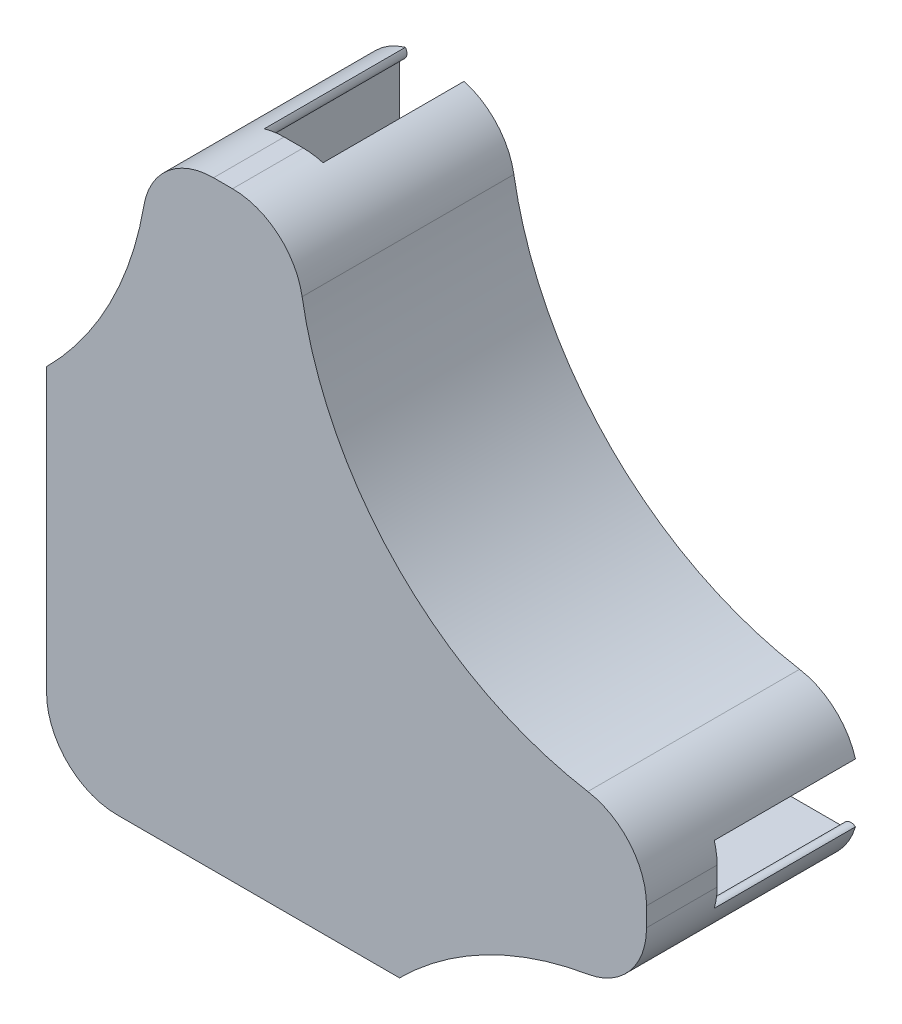
SolidWorks part; units mm, degrees
ref_plane "Front Plane" through (0, 0, 0) normal (0, 0, 1) x (1, 0, 0)
ref_plane "Top Plane" through (0, 0, 0) normal (0, 1, 0) x (1, 0, 0)
ref_plane "Right Plane" through (0, 0, 0) normal (1, 0, 0) x (0, 0, -1)
sketch "Sketch2" plane through (0, 0, 0) normal (0, 0, 1) x (1, 0, 0)
  line L0 (0, 12.7) -> (0, -12.7) construction
  line L1 (-12.7, 0) -> (12.7, 0) construction
  line L2 (3.2512, -12.7) -> (12.7, -12.7)
  line L3 (12.7, -12.7) -> (12.7, -3.2512)
  line L4 (3.2512, -12.7) -> (3.2512, -10.4902)
  line L5 (3.2512, -10.4902) -> (8.9276, -10.4902)
  line L6 (8.9276, -10.4902) -> (3.0856, -4.6482)
  line L7 (0, 0) -> (12.7, -12.7) construction
  line L8 (12.7, -3.2512) -> (10.4902, -3.2512)
  line L9 (10.4902, -3.2512) -> (10.4902, -8.9276)
  line L10 (10.4902, -8.9276) -> (4.6482, -3.0856)
  circle A0 centre (0, 0) radius 2.6035
  arc A1 (6.3485, -10.4902) -> (7.1039, -8.6665) centre (6.3485, -9.4219) ccw construction
  point P8 (0, -4.6482)
  dimension "Center Hole Diameter" = 5.207
  dimension "Rail Height" = 25.4
  dimension "Rail Width" = 25.4
  dimension "T-Slot Width" = 6.5024
  dimension "Slot Inner Width" = 14.8336
  dimension "Thickness" = 2.2098
  dimension "Slot Depth" = 5.842
  dimension "D1" = 2.2098
sketch "Sketch3" plane through (0, 0, 0) normal (1, 0, 0) x (0, 0, -1)
  line L0 (-139.7, -12.7) -> (139.7, -12.7) construction
  line L1 (-114.3, 0) -> (114.3, 0) construction
  dimension "D1" = 25.4
  dimension "Length" = 279.4
sketch "Sketch4" plane through (0, 0, 0) normal (0, 0, 1) x (1, 0, 0)
  line L0 (4.1904, -12.7) -> (10.1173, -12.7)
  line L1 (3.2512, -12.7) -> (12.7, -12.7) construction
  line L2 (3.2512, -12.7) -> (3.2512, -10.4902) construction
  line L3 (3.2512, -10.4902) -> (8.9276, -10.4902) construction
  line L4 (3.2512, -11.4294) -> (3.2512, -11.7608) construction
  line L5 (4.1904, -10.4902) -> (6.3485, -10.4902) construction
  line L6 (0, -4.6482) -> (2.164, -4.6482) construction
  line L7 (8.9276, -10.4902) -> (3.0856, -4.6482) construction
  line L8 (3.7373, -5.2999) -> (7.1039, -8.6665) construction
  line L9 (12.7, -12.7) -> (12.7, -3.2512) construction
  line L10 (10.4902, -8.9276) -> (4.6482, -3.0856) construction
  line L11 (10.4902, -3.2512) -> (10.4902, -8.9276) construction
  line L12 (10.4902, -6.3485) -> (10.4902, -4.1904) construction
  line L13 (12.7, -3.2512) -> (10.4902, -3.2512) construction
  line L14 (11.4294, -3.2512) -> (11.7608, -3.2512) construction
  line L15 (12.7, -4.1904) -> (12.7, -10.1173)
  line L16 (8.6665, -7.1039) -> (5.2999, -3.7373) construction
  line L17 (4.6482, 0) -> (4.6482, -2.164) construction
  line L18 (-12.7, 0) -> (12.7, 0) construction
  line L19 (0, -4.6482) -> (0, -2.6035) construction
  line L20 (0, 12.7) -> (0, -12.7) construction
  line L21 (4.6482, 0) -> (2.6035, 0) construction
  line L22 (4.1904, -13.335) -> (10.1173, -13.335) construction
  line L23 (13.335, -4.1904) -> (13.335, -10.1173) construction
  line L24 (11.4294, -2.6162) -> (11.7608, -2.6162)
  line L25 (9.8552, -6.3485) -> (9.8552, -4.1904)
  line L26 (9.1155, -6.6549) -> (5.7489, -3.2883)
  line L27 (5.2832, 0.635) -> (5.2832, -2.164)
  line L28 (5.2832, 0.635) -> (1.8633, 0.635)
  line L29 (-0.635, -5.2832) -> (-0.635, -1.8633)
  line L30 (-0.635, -5.2832) -> (2.164, -5.2832)
  line L31 (3.2883, -5.7489) -> (6.6549, -9.1155)
  line L32 (4.1904, -9.8552) -> (6.3485, -9.8552)
  line L33 (2.6162, -11.4294) -> (2.6162, -11.7608)
  line L34 (2.6162, -11.7608) -> (2.6162, -12.7)
  line L35 (2.6162, -12.7) -> (4.1904, -12.7)
  line L36 (12.7, -4.1904) -> (12.7, -2.6162)
  line L37 (11.7608, -2.6162) -> (12.7, -2.6162)
  line L38 (11.4294, -2.6162) -> (9.8552, -2.6162)
  line L41 (2.6162, -9.8552) -> (2.6162, -11.4294)
  line L42 (10.1173, -12.7) -> (12.7, -12.7)
  line L43 (12.7, -12.7) -> (12.7, -10.1173)
  line L44 (9.8552, -2.6162) -> (9.8552, -4.1904)
  line L45 (4.1904, -9.8552) -> (2.6162, -9.8552)
  arc A0 (3.2512, -11.7608) -> (4.1904, -12.7) centre (4.1904, -11.7608) ccw construction
  arc A1 (10.1173, -13.335) -> (13.335, -10.1173) centre (10.1173, -10.1173) ccw construction
  arc A2 (3.2512, -11.4294) -> (4.1904, -10.4902) centre (4.1904, -11.4294) cw construction
  arc A3 (6.3485, -10.4902) -> (7.1039, -8.6665) centre (6.3485, -9.4219) ccw construction
  arc A4 (2.164, -4.6482) -> (3.7373, -5.2999) centre (2.164, -6.8732) cw construction
  arc A5 (10.1173, -12.7) -> (12.7, -10.1173) centre (10.1173, -10.1173) ccw construction
  arc A6 (8.6665, -7.1039) -> (10.4902, -6.3485) centre (9.4219, -6.3485) ccw construction
  arc A7 (10.4902, -4.1904) -> (11.4294, -3.2512) centre (11.4294, -4.1904) cw construction
  arc A8 (11.7608, -3.2512) -> (12.7, -4.1904) centre (11.7608, -4.1904) cw construction
  arc A9 (5.2999, -3.7373) -> (4.6482, -2.164) centre (6.8732, -2.164) cw construction
  circle A10 centre (0, 0) radius 2.6035 construction
  arc A11 (0, -2.6035) -> (2.6035, 0) centre (0, 0) ccw construction
  arc A12 (11.7608, -2.6162) -> (13.335, -4.1904) centre (11.7608, -4.1904) cw construction
  arc A13 (9.8552, -4.1904) -> (11.4294, -2.6162) centre (11.4294, -4.1904) cw construction
  arc A14 (9.1155, -6.6549) -> (9.8552, -6.3485) centre (9.4219, -6.3485) ccw
  arc A15 (5.7489, -3.2883) -> (5.2832, -2.164) centre (6.8732, -2.164) cw
  arc A16 (-0.635, -1.8633) -> (1.8633, 0.635) centre (0, 0) ccw
  arc A17 (2.164, -5.2832) -> (3.2883, -5.7489) centre (2.164, -6.8732) cw
  arc A18 (6.3485, -9.8552) -> (6.6549, -9.1155) centre (6.3485, -9.4219) ccw
  arc A19 (2.6162, -11.4294) -> (4.1904, -9.8552) centre (4.1904, -11.4294) cw construction
  arc A20 (2.6162, -11.7608) -> (4.1904, -13.335) centre (4.1904, -11.7608) ccw construction
  dimension "D1" = 2.5827
  dimension "D2" = 2.225
  dimension "D3" = 0.9392
  dimension "D4" = 0.635
sketch "Sketch5" plane through (0, 0, 0) normal (0, 0, 1) x (1, 0, 0)
  line L0 (12.7, -4.1904) -> (12.7, -10.1173) construction
  line L1 (-15.875, 15.875) -> (15.875, 15.875) construction
  line L2 (-15.875, 15.875) -> (-15.875, -15.875)
  line L3 (-15.875, -15.875) -> (15.875, -15.875)
  line L4 (15.875, 15.875) -> (15.875, -15.875) construction
  line L5 (-15.875, 15.875) -> (15.875, -15.875) construction
  line L6 (-15.875, -15.875) -> (15.875, 15.875) construction
  line L8 (-6.6691, 38.1) -> (6.6691, 38.1)
  line L10 (38.1, -6.6691) -> (38.1, 6.6691)
  line L11 (6.6691, 38.1) -> (6.6691, 15.875) construction
  line L12 (38.1, 6.6691) -> (15.875, 6.6691) construction
  line L13 (-6.6691, 38.1) -> (-6.6691, 15.875) construction
  line L14 (38.1, -6.6691) -> (15.875, -6.6691) construction
  line L15 (0, 38.1) -> (0, 15.875) construction
  line L16 (38.1, 0) -> (15.875, 0) construction
  arc A0 (6.6691, 38.1) -> (38.1, 6.6691) centre (38.1, 38.1) ccw
  arc A1 (-6.6691, 38.1) -> (-15.875, 15.875) centre (-38.1, 38.1) cw
  arc A2 (38.1, -6.6691) -> (15.875, -15.875) centre (38.1, -38.1) ccw
  point P0 (0, 0)
  dimension "D1" = 3.175
  dimension "D2" = 25.4
extrude "Boss-Extrude1" add sketch "Sketch5" along normal blind 19.05 contours L8 A0 L10 A2 L3 L2 A1
extrude "Cut-Extrude1" cut sketch "Sketch4" along normal blind 12.7
mirror "Mirror1" about plane through (0, 0, 0) normal (0, 1, 0) of "Cut-Extrude1"
mirror "Mirror2" about plane through (0, 0, 0) normal (1, 0, 0) of "Mirror1"
sketch "Sketch6" plane through (0, 0, 0) normal (0, 0, -1) x (-1, 0, 0)
  line L0 (6.6691, 38.1) -> (-6.6691, 38.1) construction
  line L1 (-3.175, 5.2832) -> (3.175, 5.2832)
  line L2 (-3.175, 5.2832) -> (-3.175, 38.1)
  line L3 (-3.175, 38.1) -> (3.175, 38.1)
  line L4 (3.175, 5.2832) -> (3.175, 38.1)
  line L5 (-38.1, -6.6691) -> (-38.1, 6.6691) construction
  line L6 (-38.1, 3.175) -> (-5.2832, 3.175)
  line L7 (-38.1, 3.175) -> (-38.1, -3.175)
  line L8 (-38.1, -3.175) -> (-5.2832, -3.175)
  line L9 (-5.2832, 3.175) -> (-5.2832, -3.175)
  line L12 (2.164, 5.2832) -> (-2.164, 5.2832) construction
  line L13 (-5.2832, -2.164) -> (-5.2832, 2.164) construction
  line L14 (2.164, 5.2832) -> (-2.164, 5.2832) construction
  point P17 (0, 5.2832)
  point P33 (-5.2832, 0)
  dimension "D1" = 6.35
extrude "Cut-Extrude2" cut sketch "Sketch6" against normal up to surface (12.7 mm away) up to face at (0, 0, 12.7)
sketch "Sketch7" plane through (0, 0, 0) normal (0, 0, -1) x (-1, 0, 0)
  line L0 (-12.7, 3.175) -> (-38.1, 3.175) construction
  line L1 (-38.1, -3.175) -> (-12.7, -3.175) construction
  line L2 (-3.175, 38.1) -> (-3.175, 12.7) construction
  line L3 (3.175, 12.7) -> (3.175, 38.1) construction
  line L4 (-3.175, 38.1) -> (-3.175, 12.7) construction
  line L5 (-38.1, 3.175) -> (-38.1, 6.6691) construction
  line L6 (6.6691, 38.1) -> (3.175, 38.1) construction
  line L7 (-12.7, 12.7) -> (-12.7, 3.175) construction
  line L8 (-3.175, 12.7) -> (-12.7, 12.7) construction
  line L9 (3.175, 12.7) -> (3.175, 38.1) construction
  line L12 (-38.1, -3.175) -> (-12.7, -3.175) construction
  line L13 (-12.7, 3.175) -> (-38.1, 3.175) construction
  line L14 (-2.5, 37.425) -> (2.5, 37.425) construction
  circle A0 centre (-37.425, 3.175) radius 0.675
  circle A1 centre (-13.375, 3.175) radius 0.675
  circle A2 centre (-13.375, -3.175) radius 0.675
  circle A3 centre (-37.425, -3.175) radius 0.675
  circle A4 centre (-3.175, 13.375) radius 0.675
  circle A5 centre (3.175, 13.375) radius 0.675
  circle A6 centre (-3.175, 37.425) radius 0.675
  circle A7 centre (3.175, 37.425) radius 0.675
  circle A8 centre (-25.4, 3.175) radius 0.675
  circle A9 centre (-25.4, -3.175) radius 0.675
  circle A10 centre (-3.175, 25.4) radius 0.675
  circle A11 centre (3.175, 25.4) radius 0.675
  dimension "D1" = 5
extrude "Boss-Extrude2" add sketch "Sketch7" against normal up to surface (12.7 mm away) up to face at (8.0644, -4.578, 12.7)
fillet "Fillet2" radius 6.35 5 edges at (38.1, -6.6691, 9.525) (38.1, 6.6691, 9.525) (-6.6691, 38.1, 9.525) (6.6691, 38.1, 9.525) (-15.875, -15.875, 9.525)
sketch "Sketch8" plane through (0, 0, 0) normal (0, 0, -1) x (-1, 0, 0)
  line L0 (-11.1157, 10.6644) -> (-11.1157, -10.2903)
  line L1 (-11.1157, -10.2903) -> (-3.4701, -3.9897)
  line L2 (-3.4701, -3.9897) -> (-3.4701, 3.5144)
  line L3 (-3.4701, 3.5144) -> (3.6092, 3.5144)
  line L4 (3.6092, 3.5144) -> (10.0514, 10.6644)
  line L5 (10.0514, 10.6644) -> (-11.1157, 10.6644)
  point P5 (-11.1157, -10.2903)
extrude "Cut-Extrude3" cut sketch "Sketch8" against normal up to surface (12.7 mm away) up to face at (8.0644, -4.578, 12.7)
equation "\"D1@Sketch2\"=\"Thickness@Sketch2\""
equation "\"D2@Sketch4\"=\"Slot Inner Width@Sketch2\"*0.15"
equation "\"D1@Sketch4\"=\"D3@Sketch4\"*2.75"
equation "\"D3@Sketch4\"=\"Thickness@Sketch2\"*0.425"
